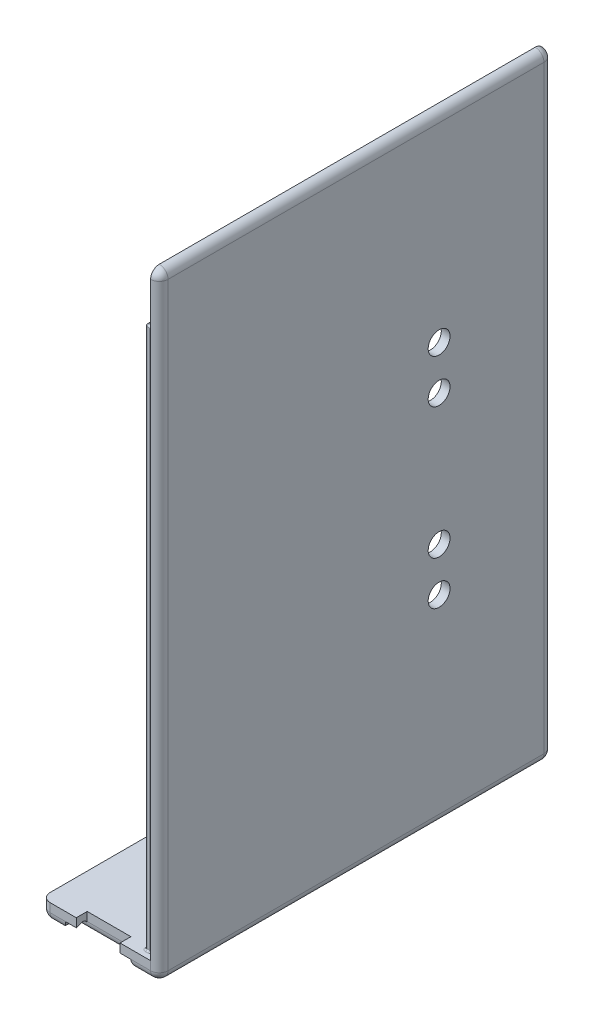
SolidWorks part; units mm, degrees
note: The reader was unsure of these and kept them because the rebuilt part matched: shared geometry of "Sketch6<3>".
ref_plane "Front Plane" through (0, 0, 0) normal (0, 0, 1) x (1, 0, 0)
ref_plane "Top Plane" through (0, 0, 0) normal (0, 1, 0) x (1, 0, 0)
ref_plane "Right Plane" through (0, 0, 0) normal (1, 0, 0) x (0, 0, -1)
sketch "Sketch1" plane through (0, 0, 0) normal (0, 1, 0) x (1, 0, 0)
  line L1 (0, 0) -> (-25, 0)
  line L2 (0, 0) -> (0, -90)
  line L3 (0, -90) -> (-25, -90)
  line L4 (-25, 0) -> (-25, -90)
  dimension "D1" = 90
  dimension "D2" = 25
extrude "Boss-Extrude1" add sketch "Sketch1" along normal blind 4
sketch "Sketch3" plane through (0, 0, 0) normal (1, 0, 0) x (0, 0, -1)
  line L1 (-90, 0) -> (0, 0)
  line L2 (-90, 0) -> (-90, 4)
  line L3 (-90, 4) -> (0, 4)
  line L4 (0, 0) -> (0, 4)
extrude "Boss-Extrude2" add sketch "Sketch3" along normal blind 2
sketch "Sketch4" plane through (0, 4, 0) normal (0, 1, 0) x (1, 0, 0)
  line L1 (2, -90) -> (0, -90)
  line L2 (2, -90) -> (2, 0)
  line L3 (2, 0) -> (0, 0)
  line L4 (0, -90) -> (0, 0)
extrude "Boss-Extrude3" add sketch "Sketch4" along normal blind 137
sketch "Sketch6" plane through (0, 0, 0) normal (0, -1, 0) x (1, 0, 0)
  line L0 (-25, 90) -> (2, 90) construction
  line L1 (-7, 90) -> (-17, 90)
  line L2 (-7, 90) -> (-7, 87.5)
  line L3 (-7, 87.5) -> (-17, 87.5)
  line L4 (-17, 90) -> (-17, 87.5)
  line L5 (2, 0) -> (-25, 0) construction
  line L6 (-7, 0) -> (-17, 0)
  line L7 (-7, 0) -> (-7, 2.5)
  line L8 (-7, 2.5) -> (-17, 2.5)
  line L9 (-17, 0) -> (-17, 2.5)
  line L10 (-25, 0) -> (-25, 90) construction
  dimension "D1" = 2.5
  dimension "D2" = 2.5
  dimension "D3" = 10
  dimension "D4" = 10
  dimension "D5" = 8
  dimension "D6" = 8
extrude "Cut-Extrude1" cut sketch "Sketch6" against normal through all contours L8 L9 L6 L7
extrude "Cut-Extrude2" cut sketch "Sketch6<3>" against normal blind 80 contours L3 L4 L1 L2
sketch "Sketch6<3>" plane through (0, 0, 0) normal (0, -1, 0) x (1, 0, 0) same geometry as "Sketch6"
sketch "Sketch8" plane through (0, 0, 90) normal (0, 0, 1) x (1, 0, 0)
  line L0 (-7, 0) -> (2, 0) construction
  line L1 (-4.5, 0) -> (-19.5, 0)
  line L2 (-4.5, 0) -> (-4.5, 2)
  line L3 (-4.5, 2) -> (-19.5, 2)
  line L4 (-19.5, 0) -> (-19.5, 2)
  line L5 (-25, 4) -> (-25, 0) construction
  dimension "D1" = 2
  dimension "D2" = 15
  dimension "D3" = 5.5
extrude "Cut-Extrude3" cut sketch "Sketch8" against normal blind 2.5
sketch "Sketch9" plane through (-4.5, 0, 0) normal (-1, 0, 0) x (0, 0, 1)
  line L0 (90, 0) -> (90, 2) construction
  line L1 (87.5, 2) -> (90, 2) construction
  line L2 (88.5, 2.5) -> (90, 2)
  line L3 (90, 2) -> (88.5, 2)
  line L4 (88.5, 2) -> (88.5, 2.5)
  circle A0 centre (88.5, 1.5) radius 1
  line M3 (90, 2) -> (87.5, 2)
  dimension "D1" = 2
  dimension "D2" = 1.5
  dimension "D3" = 0.5
extrude "Cut-Extrude5" cut sketch "Sketch9" along a picked direction on the side of the normal blind 15 contours A0 L3 M3 | L4 A0 M3
sketch "Sketch10" plane through (0, 0, 0) normal (0, -1, 0) x (1, 0, 0)
  line L0 (2, 45) -> (-25, 45) construction
  line L1 (2, 90) -> (2, 0) construction
  line L2 (-25, 0) -> (-25, 90) construction
  line L3 (-25, 45) -> (2, 45) construction
sketch "Sketch11" plane through (0, 0, 0) normal (0, 0, -1) x (-1, 0, 0)
  line L0 (-2, 0) -> (7, 0) construction
  line L1 (4.5, 0) -> (19.5, 0)
  line L2 (4.5, 0) -> (4.5, 2)
  line L3 (4.5, 2) -> (19.5, 2)
  line L4 (19.5, 0) -> (19.5, 2)
  line L5 (25, 4) -> (25, 0) construction
  dimension "D1" = 2
  dimension "D2" = 15
  dimension "D3" = 5.5
extrude "Cut-Extrude6" cut sketch "Sketch11" against normal blind 3 contours L2 L3 L4 L1
sketch "Sketch12" plane through (-4.5, 0, 0) normal (-1, 0, 0) x (0, 0, 1)
  line L0 (0, 0) -> (0, 2) construction
  line L1 (3, 2) -> (0, 2) construction
  line L2 (1.9, 2.5) -> (0, 2)
  line L3 (0, 2) -> (1.9, 2)
  line L4 (1.9, 2) -> (1.9, 2.5)
  circle A0 centre (1.9, 1.5) radius 1
  line M4 (3, 2) -> (0, 2)
  dimension "D1" = 2
  dimension "D2" = 1.9
  dimension "D3" = 0.5
extrude "Cut-Extrude7" cut sketch "Sketch12" along normal blind 15 contours A0 M4 | A0 L4 M4
fillet "Fillet6" radius 2 11 edges at (-19.5, 0, 1.5) (-1.25, 0, 0) (-25, 0, 45) (-22.25, 0, 90) (-19.5, 0, 88.75) (-12, 0, 87.5) (-4.5, 0, 88.75) (-1.25, 0, 90) (2, 0, 45) (-4.5, 0, 1.5) (-12, 0, 3)
fillet "Fillet7" radius 2 4 edges at (-24.4142, 0.5858, 89.4142) (-24.4142, 0.5858, 0.5858) (-25, 3, 90) (-25, 3, 0)
sketch "Sketch13" plane through (0, 4, 0) normal (0, 1, 0) x (1, 0, 0)
  line L6 (0, -4.05) -> (-1.4, -4.05)
  line L7 (0, 0) -> (0, -90) construction
  line L8 (-1.4, -4.05) -> (-1.4, -1.6)
  line L9 (-1.4, -1.6) -> (-2.8, -1.6)
  line L10 (-2.8, -1.6) -> (-2.8, -5.4)
  line L11 (-2.8, -5.4) -> (0, -5.4)
  line L12 (0, 0) -> (-7, 0) construction
  line L13 (0, -4.05) -> (0, -5.4)
  line L14 (0, -45) -> (-25.0562, -45) construction
  line L15 (-1.4, -88.4) -> (-2.8, -88.4)
  line L16 (-2.8, -88.4) -> (-2.8, -84.6)
  line L17 (-2.8, -84.6) -> (0, -84.6)
  line L18 (0, -85.95) -> (0, -84.6)
  line L19 (0, -85.95) -> (-1.4, -85.95)
  line L20 (-1.4, -85.95) -> (-1.4, -88.4)
  dimension "D1" = 1.4
  dimension "D2" = 1.4
  dimension "D3" = 1.6
  dimension "D4" = 3.8
  dimension "D5" = 1.35
extrude "Boss-Extrude4" add sketch "Sketch13" along normal blind 124
fillet "Fillet8" radius 0.4 24 edges at (-1.4, 4, 2.825) (0, 128, 4.725) (0, 128, 85.275) (-1.4, 4, 87.175) (-1.4, 66, 1.6) (-2.1, 128, 1.6) (-2.1, 4, 1.6) (-2.8, 66, 1.6) (-2.8, 128, 3.5) (-2.8, 4, 3.5) (-2.8, 66, 5.4) (-1.4, 128, 5.4) (0, 66, 5.4) (-1.4, 4, 5.4) (0, 66, 84.6) (-1.4, 128, 84.6) (-1.4, 4, 84.6) (-2.8, 66, 84.6) (-2.8, 128, 86.5) (-2.8, 4, 86.5) (-2.8, 66, 88.4) (-2.1, 128, 88.4) (-1.4, 66, 88.4) (-2.1, 4, 88.4)
fillet "Fillet9" radius 2 7 edges at (2, 71.5, 90) (2, 71.5, 0) (1.4142, 0.5858, 89.4142) (1.4142, 0.5858, 0.5858) (2, 141, 45) (1, 141, 0) (1, 141, 90)
sketch "Sketch14" plane through (0, 0, 0) normal (0, -1, 0) x (1, 0, 0)
  line L0 (-18.6192, 85.5) -> (-18.6192, 5) construction
  line L4 (-2.5, 85.5) -> (-21.5, 85.5) construction
  line L5 (-21.5, 5) -> (-2.5, 5) construction
  text T0 "RESP\r\n" font "Century Gothic" height in points 48
sketch "Sketch15" plane through (2, 0, 0) normal (1, 0, 0) x (0, 0, -1)
  line L0 (-40, 139) -> (-40, 2) construction
  line L1 (-2, 139) -> (-88, 139) construction
  line L2 (-88, 2) -> (-2, 2) construction
  line L3 (0, 139) -> (0, 4) construction
  text T0 "CONTROLLER" font "Century Gothic" height in points 36
  dimension "D1" = 40
sketch "Sketch16" plane through (2, 0, 0) normal (1, 0, 0) x (0, 0, -1)
  line L0 (-25.9862, 139) -> (-25.9862, 2) construction
  line L1 (-2, 139) -> (-88, 139) construction
  line L2 (-88, 2) -> (-2, 2) construction
  circle A0 centre (-25.9862, 95.5) radius 2.5
  circle A1 centre (-25.9862, 85.5) radius 2.5
  circle A2 centre (-25.9862, 55.5) radius 2.5
  circle A3 centre (-25.9862, 45.5) radius 2.5
  dimension "D1" = 5
  dimension "D2" = 5
  dimension "D5" = 5
  dimension "D6" = 5
  dimension "D3" = 10
  dimension "D4" = 10
  dimension "D7" = 30
  dimension "D8" = 43.5
  dimension "D9" = 43.5
extrude "Cut-Extrude8" cut sketch "Sketch16" against normal blind 10
